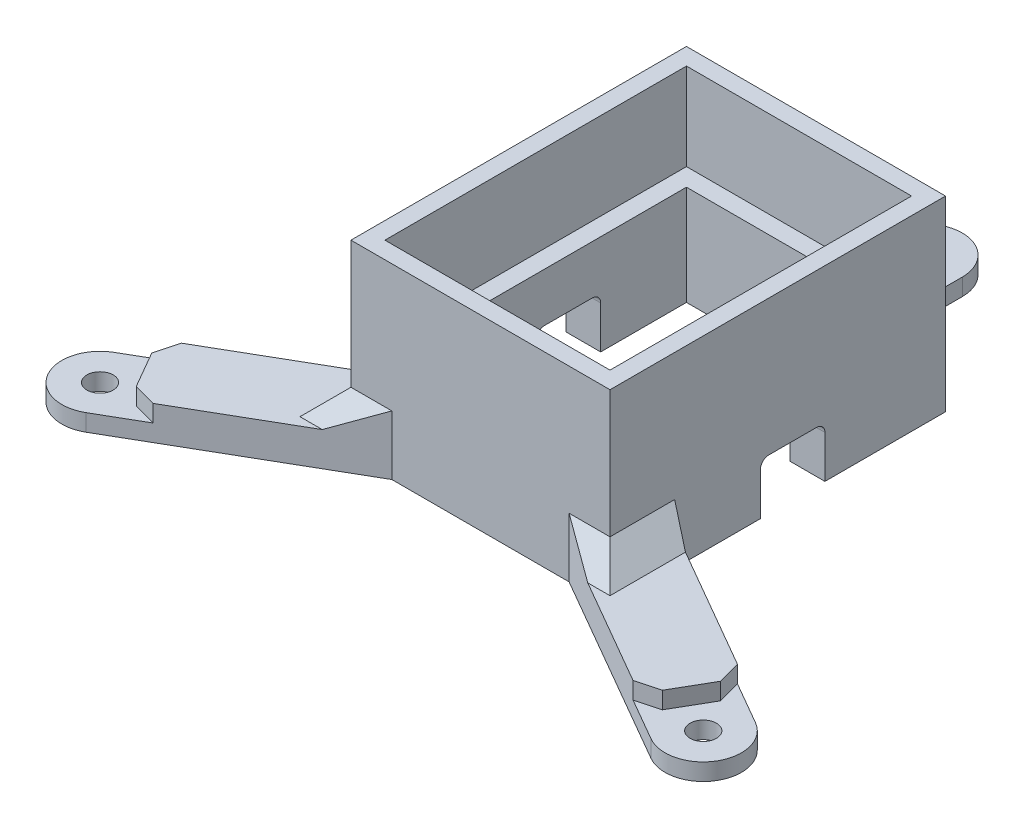
SolidWorks part; units mm, degrees
ref_plane "Front Plane" through (0, 0, 0) normal (0, 0, 1) x (1, 0, 0)
ref_plane "Top Plane" through (0, 0, 0) normal (0, 1, 0) x (1, 0, 0)
ref_plane "Right Plane" through (0, 0, 0) normal (1, 0, 0) x (0, 0, -1)
sketch "Sketch1" plane through (0, 0, 0) normal (0, 1, 0) x (1, 0, 0)
  line L0 (15.25, 19.75) -> (-15.25, 19.75)
  line L1 (13.25, -17.75) -> (-13.25, -17.75)
  line L2 (13.25, -17.75) -> (13.25, 17.75)
  line L3 (13.25, 17.75) -> (-13.25, 17.75)
  line L4 (-13.25, -17.75) -> (-13.25, 17.75)
  line L5 (13.25, -17.75) -> (-13.25, 17.75) construction
  line L6 (13.25, 17.75) -> (-13.25, -17.75) construction
  line L7 (-15.25, -19.75) -> (-15.25, 19.75)
  line L8 (15.25, -19.75) -> (-15.25, -19.75)
  line L9 (15.25, -19.75) -> (15.25, 19.75)
  point P0 (0, 0)
  dimension "D1" = 35.5
  dimension "D2" = 26.5
  dimension "D3" = 2
extrude "Boss-Extrude1" add sketch "Sketch1" along normal blind 22
sketch "Sketch3" plane through (0, 0, 0) normal (0, -1, 0) x (1, 0, 0)
  line L1 (-13.25, 17.75) -> (13.25, 17.75)
  line L2 (-13.25, 17.75) -> (-13.25, -17.75)
  line L3 (-13.25, -17.75) -> (13.25, -17.75)
  line L4 (13.25, 17.75) -> (13.25, -17.75)
  line L12 (-11.15, 15.65) -> (-11.15, -15.65)
  line L13 (11.15, 15.65) -> (-11.15, 15.65)
  line L14 (11.15, -15.65) -> (11.15, 15.65)
  line L15 (-11.15, -15.65) -> (11.15, -15.65)
  line L16 (-11.15, 15.65) -> (-11.15, -15.65)
  line L17 (11.15, 15.65) -> (-11.15, 15.65)
  line L18 (11.15, -15.65) -> (11.15, 15.65)
  line L19 (-11.15, -15.65) -> (11.15, -15.65)
  dimension "D1" = 2.1
extrude "Boss-Extrude3" add sketch "Sketch3" against normal blind 11.75
sketch "Sketch4" plane through (0, 22, 0) normal (0, 1, 0) x (1, 0, 0)
  line L1 (-15.25, 19.75) -> (-15.25, -19.75) construction
  line L2 (0, -8.53) -> (-35.507, -29.03) construction
  line L6 (-33.257, -32.9271) -> (-10.4336, -19.75)
  line L7 (-15.25, -19.75) -> (15.25, -19.75) construction
  line L10 (-15.25, -12.1384) -> (-37.757, -25.1329)
  line L11 (0, 0) -> (0, -8.53) construction
  line L12 (15.25, 19.75) -> (-15.25, 19.75) construction
  line L13 (-4.5, 19.75) -> (4.5, 19.75)
  line L14 (-4.5, 19.75) -> (-4.5, 32.47)
  line L15 (-4.5, 32.47) -> (4.5, 32.47) construction
  line L16 (4.5, 19.75) -> (4.5, 32.47)
  line L17 (-15.25, -12.1384) -> (-15.25, -19.75)
  line L19 (-15.25, -19.75) -> (-10.4336, -19.75)
  circle A1 centre (0, -8.53) radius 41 construction
  arc A3 (-4.5, 32.47) -> (4.5, 32.47) centre (0, 32.47) cw
  circle A4 centre (-35.507, -29.03) radius 1.55
  arc A6 (-37.757, -25.1329) -> (-33.257, -32.9271) centre (-35.507, -29.03) ccw
  circle A7 centre (0, 32.47) radius 1.55
  point P23 (0, 19.75)
  dimension "D1" = 120
  dimension "D2" = 82
  dimension "D4" = 9
  dimension "D5" = 3.1
  dimension "D3" = 8.53
  dimension "D6" = 9
extrude "Boss-Extrude4" add sketch "Sketch4" along normal blind 4 from surface starting at face at (0, 0, 0)
sketch "Sketch6" plane through (0, 4, 0) normal (0, 1, 0) x (1, 0, 0)
  line L1 (-2.85, 34.1154) -> (-2.85, 30.8246)
  line L2 (-2.85, 30.8246) -> (0, 29.1791)
  line L3 (0, 29.1791) -> (2.85, 30.8246)
  line L4 (2.85, 30.8246) -> (2.85, 34.1154)
  line L5 (2.85, 34.1154) -> (0, 35.7609)
  line L6 (0, 35.7609) -> (-2.85, 34.1154)
  line L7 (-35.507, -32.3209) -> (-32.657, -30.6754)
  line L8 (-32.657, -30.6754) -> (-32.657, -27.3846)
  line L9 (-32.657, -27.3846) -> (-35.507, -25.7391)
  line L10 (-35.507, -25.7391) -> (-38.357, -27.3846)
  line L11 (-38.357, -27.3846) -> (-38.357, -30.6754)
  line L12 (-38.357, -30.6754) -> (-35.507, -32.3209)
  circle A0 centre (0, 32.47) radius 2.85 construction
  circle A1 centre (-35.507, -29.03) radius 2.85 construction
  dimension "D1" = 5.7
extrude "Cut-Extrude1" cut sketch "Sketch6" against normal offset from surface (2 mm away) 2 up to face at (-7.7586, 0, -3.3174)
mirror "Mirror1" about plane through (0, 0, 0) normal (1, 0, 0) of "Cut-Extrude1", "Boss-Extrude4"
chamfer "Chamfer2" distance 3 angle 45 5 edges at (-15.25, 4, 15.9442) (-12.8418, 4, 19.75) (0, 4, -19.75) (15.25, 4, 15.9442) (12.8418, 4, 19.75)
sketch "Sketch7" plane through (15.25, 0, 0) normal (1, 0, 0) x (0, 0, -1)
  line L0 (19.75, 22) -> (19.75, 0) construction
  line L1 (5.55, 0) -> (-2.05, 0)
  line L2 (5.55, 0) -> (5.55, 5)
  line L3 (4.55, 6) -> (-1.05, 6)
  line L4 (-2.05, 0) -> (-2.05, 5)
  line L6 (-12.1384, 0) -> (19.75, 0) construction
  line L7 (1.75, 6) -> (1.75, 0) construction
  arc A0 (5.55, 5) -> (4.55, 6) centre (4.55, 5) ccw
  arc A1 (-1.05, 6) -> (-2.05, 5) centre (-1.05, 5) ccw
  point P14 (5.55, 6)
  point P17 (-2.05, 6)
  dimension "D4" = 1
  dimension "D1" = 7.6
  dimension "D2" = 6
  dimension "D3" = 18
extrude "Cut-Extrude2" cut sketch "Sketch7" against normal through all
sketch "Sketch8" plane through (0, 4, 0) normal (0, 1, 0) x (1, 0, 0)
  line L0 (-34.474, -23.2374) -> (-29.974, -31.0317)
  line L1 (-18.25, -13.8705) -> (-37.757, -25.1329) construction
  line L2 (-33.257, -32.9271) -> (-15.6298, -22.75) construction
  line L3 (-34.474, -23.2374) -> (-37.757, -25.1329)
  line L4 (-33.257, -32.9271) -> (-29.974, -31.0317)
  line L5 (4.5, 22.75) -> (4.5, 32.47) construction
  line L6 (-4.5, 32.47) -> (-4.5, 22.75) construction
  line L7 (4.5, 28.6791) -> (4.5, 32.47)
  line L8 (-4.5, 32.47) -> (-4.5, 28.6791)
  line L9 (-4.5, 28.6791) -> (4.5, 28.6791)
  line L10 (0, 0) -> (0, 15.65) construction
  line L11 (-11.15, 15.65) -> (11.15, 15.65) construction
  line L12 (33.257, -32.9271) -> (29.974, -31.0317)
  line L13 (34.474, -23.2374) -> (37.757, -25.1329)
  line L14 (34.474, -23.2374) -> (29.974, -31.0317)
  arc A0 (-37.757, -25.1329) -> (-33.257, -32.9271) centre (-35.507, -29.03) ccw construction
  arc A1 (-37.757, -25.1329) -> (-33.257, -32.9271) centre (-35.507, -29.03) ccw
  arc A2 (4.5, 32.47) -> (-4.5, 32.47) centre (0, 32.47) ccw construction
  arc A3 (4.5, 32.47) -> (-4.5, 32.47) centre (0, 32.47) ccw
  arc A4 (37.757, -25.1329) -> (33.257, -32.9271) centre (35.507, -29.03) cw
  dimension "D1" = 0.5
  dimension "D2" = 0.5
extrude "Cut-Extrude3" cut sketch "Sketch8" against normal up to surface (2 mm away) up to face at (-35.507, 2, 30.58)
chamfer "Chamfer3" distance 2 angle 45 6 edges at (-29.974, 3, 31.0317) (-4.5, 3, -28.6791) (4.5, 3, -28.6791) (34.474, 3, 23.2374) (29.974, 3, 31.0317) (-34.474, 3, 23.2374)
